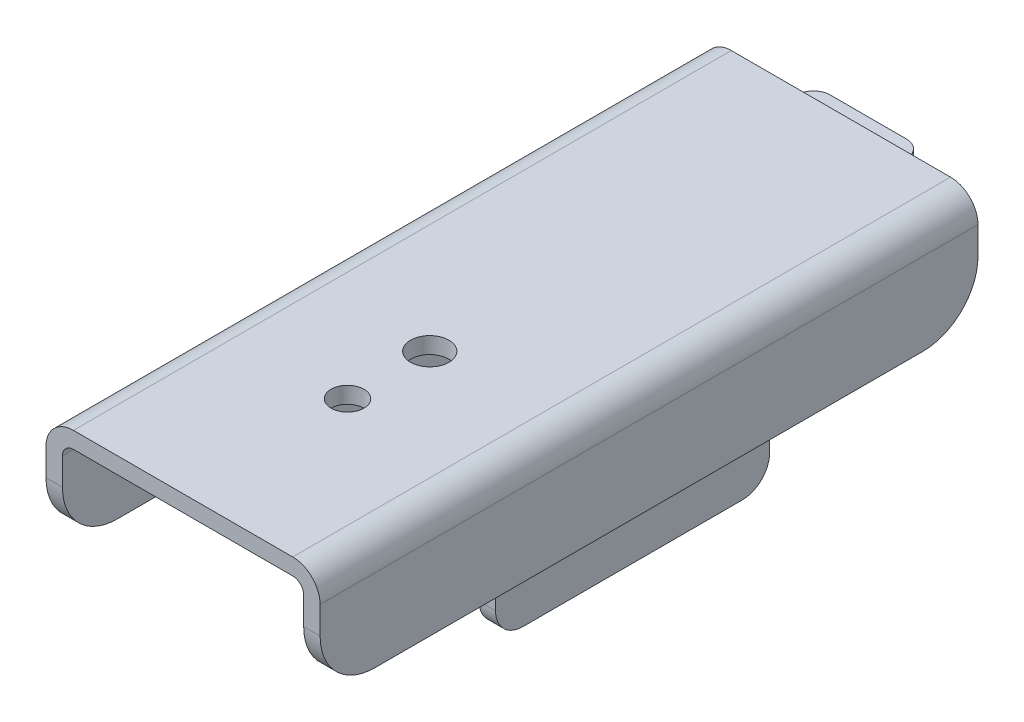
SolidWorks part; units mm, degrees
ref_plane "Front Plane" through (0, 0, 0) normal (0, 0, 1) x (1, 0, 0)
ref_plane "Top Plane" through (0, 0, 0) normal (0, 1, 0) x (1, 0, 0)
ref_plane "Right Plane" through (0, 0, 0) normal (1, 0, 0) x (0, 0, -1)
sketch "Sketch1" plane through (0, 0, 0) normal (0, 0, 1) x (1, 0, 0)
  line L16 (-48.5859, 38.4719) -> (-88.5859, 38.4719)
  line L17 (-93.5859, 33.4719) -> (-93.5859, 18.4719)
  line L18 (-93.5859, 18.4719) -> (-90.5859, 18.4719)
  line L19 (-90.5859, 18.4719) -> (-90.5859, 33.4719)
  line L20 (-88.5859, 35.4719) -> (-48.5859, 35.4719)
  line L21 (-46.5859, 33.4719) -> (-46.5859, 18.4719)
  line L22 (-46.5859, 18.4719) -> (-43.5859, 18.4719)
  line L23 (-43.5859, 18.4719) -> (-43.5859, 33.4719)
  arc A8 (-88.5859, 38.4719) -> (-93.5859, 33.4719) centre (-88.5859, 33.4719) ccw
  arc A9 (-88.5859, 35.4719) -> (-90.5859, 33.4719) centre (-88.5859, 33.4719) ccw
  arc A10 (-46.5859, 33.4719) -> (-48.5859, 35.4719) centre (-48.5859, 33.4719) ccw
  arc A11 (-43.5859, 33.4719) -> (-48.5859, 38.4719) centre (-48.5859, 33.4719) ccw
extrude "Boss-Extrude1" add sketch "Sketch1" along normal blind 120
fillet "Fillet1" radius 10 4 edges at (-92.0859, 18.4719, 0) (-45.0859, 18.4719, 0) (-92.0859, 18.4719, 120) (-45.0859, 18.4719, 120)
sketch "Sketch2" plane through (0, 18.4719, 0) normal (0, -1, 0) x (1, 0, 0)
  line L0 (-46.5859, 110) -> (-46.5859, 10) construction
  line L1 (-46.5859, 35) -> (-49.5859, 35)
  line L2 (-46.5859, 35) -> (-46.5859, 85)
  line L3 (-46.5859, 85) -> (-49.5859, 85)
  line L4 (-49.5859, 35) -> (-49.5859, 85)
  line L5 (-43.5859, 60) -> (-93.5859, 60) construction
  line L6 (-43.5859, 110) -> (-43.5859, 10) construction
  line L7 (-93.5859, 110) -> (-93.5859, 10) construction
  line L8 (-68.5859, 60) -> (-68.5859, 40.7332) construction
  line L9 (-87.5859, 35) -> (-87.5859, 85)
  line L10 (-90.5859, 85) -> (-87.5859, 85)
  line L11 (-90.5859, 35) -> (-90.5859, 85)
  line L12 (-90.5859, 35) -> (-87.5859, 35)
extrude "Boss-Extrude2" add sketch "Sketch2" against normal up to surface (17 mm away) and the other way blind 10 up to face at (-68.5859, 35.4719, 60)
sketch "Sketch3" plane through (0, 35.4719, 0) normal (0, -1, 0) x (1, 0, 0)
  line L0 (-68.5859, 0) -> (-68.5859, 20.5264) construction
  line L1 (-58.5859, 10) -> (-78.5859, 10)
  line L2 (-58.5859, 10) -> (-58.5859, -5)
  line L3 (-58.5859, -5) -> (-78.5859, -5)
  line L4 (-78.5859, 10) -> (-78.5859, -5)
  line L5 (-88.5859, 0) -> (-48.5859, 0) construction
  dimension "D1" = 10
  dimension "D2" = 20
  dimension "D3" = 15
  dimension "D4" = 10
extrude "Boss-Extrude3" add sketch "Sketch3" along normal blind 3
fillet "Fillet2" radius 5 4 edges at (-89.0859, 8.4719, 35) (-89.0859, 8.4719, 85) (-48.0859, 8.4719, 35) (-48.0859, 8.4719, 85)
chamfer "Chamfer1" distance 4 angle 45 1 edges at (-68.5859, 35.4719, 10)
fillet "Fillet3" radius 4 2 edges at (-68.5859, 35.4719, 14) (-68.5859, 32.4719, 11)
fillet "Fillet4" radius 3 2 edges at (-78.5859, 33.9719, -5) (-58.5859, 33.9719, -5)
sketch "Sketch4" plane through (0, 35.4719, 0) normal (0, -1, 0) x (1, 0, 0)
  line L0 (-46.5859, 35) -> (-46.5859, 10) construction
  line L1 (-46.5859, 20) -> (-90.5859, 20)
  line L2 (-46.5859, 20) -> (-46.5859, 23)
  line L3 (-46.5859, 23) -> (-90.5859, 23)
  line L4 (-90.5859, 20) -> (-90.5859, 23)
  line L5 (-90.5859, 35) -> (-90.5859, 10) construction
  line L6 (-46.5859, 110) -> (-46.5859, 85) construction
  line L7 (-46.5859, 100) -> (-90.5859, 100)
  line L8 (-46.5859, 100) -> (-46.5859, 97)
  line L9 (-46.5859, 97) -> (-90.5859, 97)
  line L10 (-90.5859, 100) -> (-90.5859, 97)
  line L11 (-90.5859, 110) -> (-90.5859, 85) construction
  line L12 (-88.5859, 120) -> (-48.5859, 120) construction
  line L13 (-88.5859, 0) -> (-78.5859, 0) construction
  line L14 (-68.5859, 97) -> (-68.5859, 23) construction
  line L15 (-90.5859, 80) -> (-90.5859, 40) construction
  line L16 (-90.5859, 61.5) -> (-46.5859, 61.5)
  line L17 (-90.5859, 61.5) -> (-90.5859, 58.5)
  line L18 (-90.5859, 58.5) -> (-46.5859, 58.5)
  line L19 (-46.5859, 61.5) -> (-46.5859, 58.5)
  line L20 (-46.5859, 40) -> (-46.5859, 80) construction
  line L21 (-93.5859, 60) -> (-43.5859, 60) construction
  line L22 (-93.5859, 110) -> (-93.5859, 10) construction
  line L23 (-43.5859, 110) -> (-43.5859, 10) construction
  dimension "D1" = 3
  dimension "D2" = 20
  dimension "D3" = 3
  dimension "D4" = 20
  dimension "D5" = 3
  dimension "D6" = 1.5
extrude "Boss-Extrude4" add sketch "Sketch4" along normal blind 5
fillet "Fillet5" radius 3 4 edges at (-49.5859, 35.4719, 46.75) (-49.5859, 35.4719, 73.25) (-87.5859, 35.4719, 73.25) (-87.5859, 35.4719, 46.75)
sketch "Sketch7" plane through (0, 38.4719, 0) normal (0, 1, 0) x (1, 0, 0)
  circle A0 centre (-68.5859, -75) radius 3.5
extrude "Cut-Extrude3" cut sketch "Sketch7" against normal up to surface (3 mm away) up to face at (-68.5859, 35.4719, 8.9142)
sketch "Sketch8" plane through (0, 38.4719, 0) normal (0, 1, 0) x (1, 0, 0)
  line L0 (-48.5859, -120) -> (-88.5859, -120) construction
  circle A0 centre (-68.5859, -90) radius 3
  dimension "D1" = 30
extrude "Cut-Extrude7" cut sketch "Sketch8" against normal blind 12
sketch "Sketch11" plane through (0, 35.4719, 0) normal (0, -1, 0) x (1, 0, 0)
  line L1 (-60.5859, 108) -> (-76.5859, 108)
  line L2 (-60.5859, 108) -> (-60.5859, 118)
  line L3 (-60.5859, 118) -> (-76.5859, 118)
  line L4 (-76.5859, 108) -> (-76.5859, 118)
extrude "Cut-Extrude9" cut sketch "Sketch11" against normal blind 2
